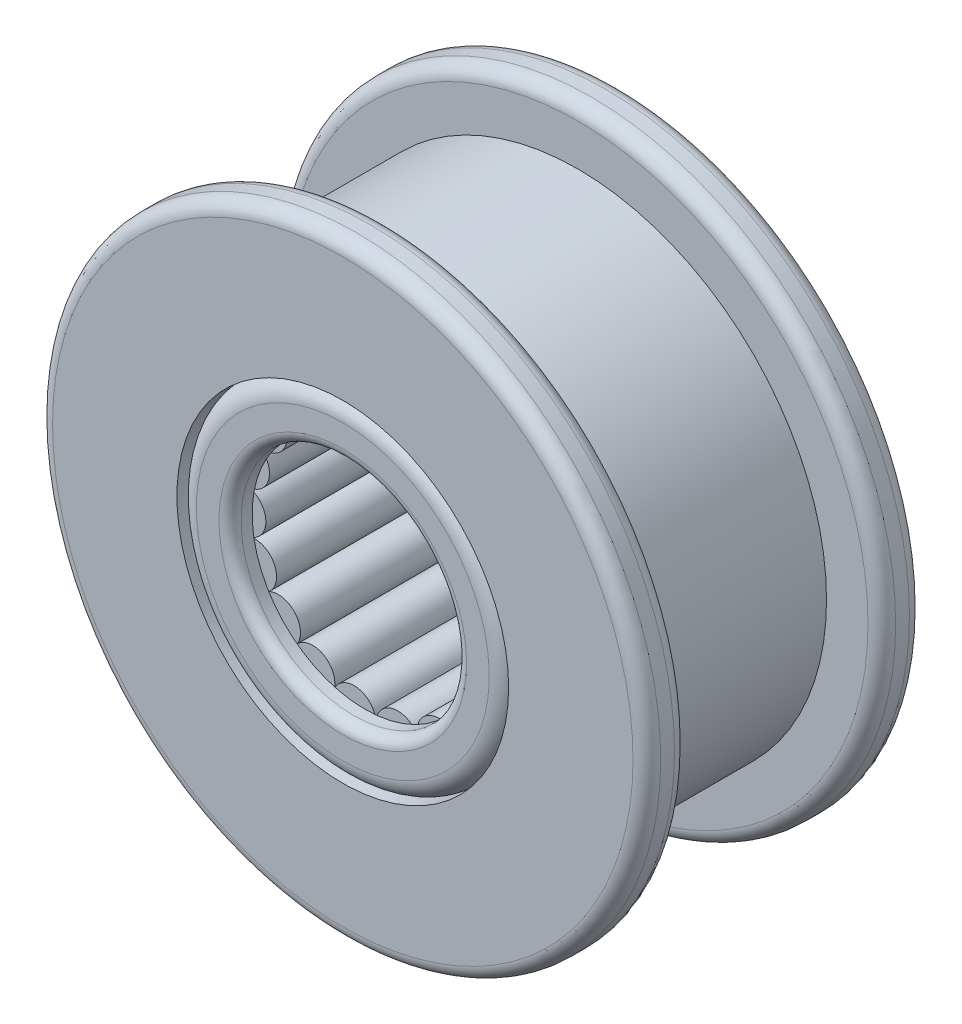
SolidWorks part; units mm, degrees
ref_plane "Front Plane" through (0, 0, 0) normal (0, 0, 1) x (1, 0, 0)
ref_plane "Top Plane" through (0, 0, 0) normal (0, 1, 0) x (1, 0, 0)
ref_plane "Right Plane" through (0, 0, 0) normal (1, 0, 0) x (0, 0, -1)
sketch "Sketch1" plane through (0, 0, 0) normal (1, 0, 0) x (0, 0, -1)
  line L0 (0, 0) -> (15.875, 0) construction
  line L1 (13.4937, 17.4625) -> (15.875, 17.4625)
  line L2 (0, 9.525) -> (15.875, 9.525)
  line L4 (0, 17.4625) -> (2.3812, 17.4625)
  line L5 (15.875, 9.525) -> (15.875, 17.4625)
  line L7 (2.3812, 17.4625) -> (2.3812, 14.2875)
  line L8 (2.3812, 14.2875) -> (13.4937, 14.2875)
  line L9 (13.4937, 17.4625) -> (13.4937, 14.2875)
  line L12 (0, 9.525) -> (0, 6.35) construction
  line L13 (0, 9.525) -> (0, 17.4625)
  line L15 (15.875, 9.525) -> (15.875, 6.35) construction
  line L16 (15.875, 6.35) -> (0, 6.35) construction
  dimension "D1" = 3.175
  dimension "A" = 34.925
  dimension "B" = 15.875
  dimension "C" = 12.7
  dimension "D" = 28.575
  dimension "E" = 11.1125
  dimension "G" = 15.875
  dimension "I" = 0
  dimension "F" = 0
revolve "Revolve1" add sketch "Sketch1" angle 360 about L0
fillet "Fillet1" radius 0.795 4 edges at (17.4625, 0, -15.875) (17.4625, 0, -13.4937) (17.4625, 0, -2.3812) (17.4625, 0, 0)
sketch "Sketch2" plane through (0, 0, 0) normal (1, 0, 0) x (0, 0, -1)
  line L0 (0, 0) -> (15.875, 0) construction
  line L1 (0, 6.477) -> (1.27, 6.477)
  line L2 (0, 6.477) -> (0, 9.525)
  line L3 (0, 9.525) -> (15.875, 9.525)
  line L4 (15.875, 6.477) -> (15.875, 9.525)
  line L6 (15.875, 6.35) -> (0, 6.35) construction
  line L7 (1.27, 6.477) -> (1.27, 8.255)
  line L8 (1.27, 8.255) -> (14.605, 8.255)
  line L9 (14.605, 8.255) -> (14.605, 6.477)
  line L10 (14.605, 6.477) -> (15.875, 6.477)
  line L11 (1.27, 8.255) -> (1.27, 9.525) construction
  dimension "D1" = 0.127
  dimension "D2" = 1.27
revolve "Revolve2" add sketch "Sketch2" angle 360 about L0
fillet "Fillet2" radius 1.1125 2 edges at (0, -9.525, 0) (0, -9.525, -15.875)
fillet "Fillet3" radius 0.635 2 edges at (0, -6.477, 0) (0, -6.477, -15.875)
sketch "Sketch3" plane through (0, 0, -1.27) normal (0, 0, 1) x (1, 0, 0)
  line L0 (0, 0) -> (-1.2522, 7.4083) construction
  line L1 (0, 0) -> (1.2522, 7.4083) construction
  circle A0 centre (0, 7.62) radius 1.27
  circle A1 centre (0, 0) radius 6.35 construction
  dimension "D2" = 19.188
extrude "Boss-Extrude1" add sketch "Sketch3" against normal offset from surface (12.065 mm away) 0.635 from offset 0.635 separate body up to face at (0, -6.477, -14.605) offset against normal yes
pattern_circular "CirPattern1" count 19 over 360 about axis through (0, 0, 0) along (0, 0, 1) of bodies 104
equation "\"D1@CirPattern1\" = \"D3@CirPattern1\" / \"D2@Sketch3\""
